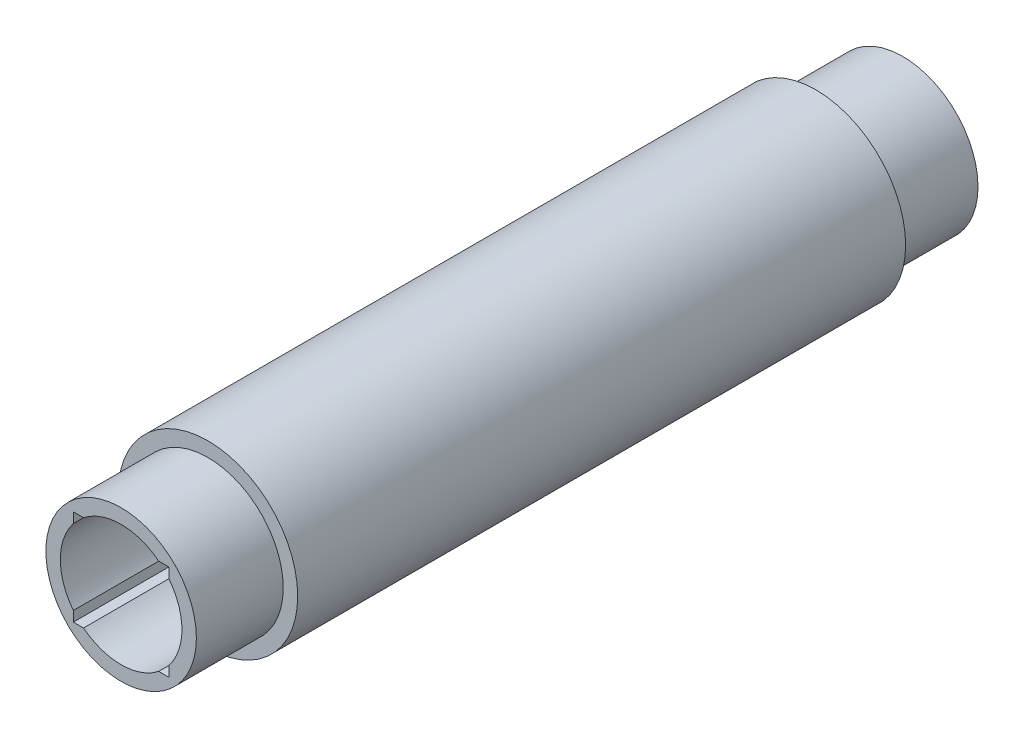
SolidWorks part; units mm, degrees
ref_plane "Front" through (0, 0, 0) normal (0, 0, 1) x (1, 0, 0)
ref_plane "Top" through (0, 0, 0) normal (0, 1, 0) x (1, 0, 0)
ref_plane "Right" through (0, 0, 0) normal (1, 0, 0) x (0, 0, -1)
sketch "Sketch1" plane through (0, 0, 0) normal (0, 0, 1) x (1, 0, 0)
  circle A0 centre (0, 0) radius 5.2
  circle A1 centre (0, 0) radius 4.2
  circle A2 centre (0, 0) radius 6.2
  dimension "D1" = 1
  dimension "D2" = 8.4
  dimension "D3" = 1
extrude "Boss-Extrude2" add sketch "Sketch1" along normal mid plane 54 contours A0 | A1
extrude "Boss-Extrude3" add sketch "Sketch1<3>" along normal mid plane 42 contours A2 A0 region at (-6.0246, 0, 0)
sketch "Sketch1<3>" plane through (0, 0, 0) normal (0, 0, 1) x (1, 0, 0) same geometry as "Sketch1"
sketch "Sketch3" plane through (0, 0, 0) normal (0, 0, 1) x (1, 0, 0)
  line L1 (-3.3, 3.3) -> (3.3, 3.3)
  line L2 (-3.3, 3.3) -> (-3.3, -3.3)
  line L3 (-3.3, -3.3) -> (3.3, -3.3)
  line L4 (3.3, 3.3) -> (3.3, -3.3)
  line L5 (-3.3, 3.3) -> (3.3, -3.3) construction
  line L6 (-3.3, -3.3) -> (3.3, 3.3) construction
  point P0 (0, 0)
  dimension "D1" = 6.6
extrude "Cut-Extrude1" cut sketch "Sketch3" against normal blind 15 from surface contours L1 L4 L3 L2 starting at face at (5.2, 0, 27)
extrude "Cut-Extrude2" cut sketch "Sketch3<3>" along normal blind 15 from surface starting at face at (5.2, 0, -27)
sketch "Sketch3<3>" plane through (0, 0, 0) normal (0, 0, 1) x (1, 0, 0) same geometry as "Sketch3"
equation "\"Coil Space\"= \"D1@Boss-Extrude3\""
equation "\"Standoff Depth\"= 6"
equation "\"Part Length\"= \"D1@Boss-Extrude3\""
equation "\"D1@Boss-Extrude2\"= \"Coil Space\" + 2 * \"Standoff Depth\""
